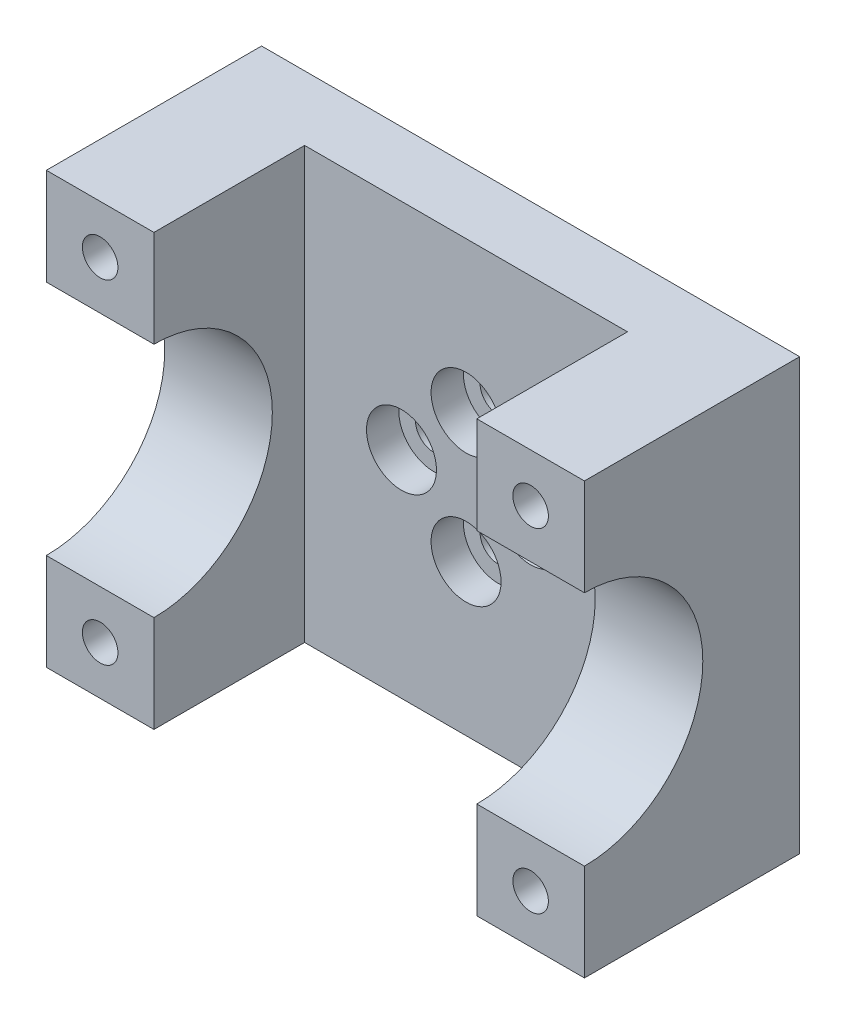
SolidWorks part; units mm, degrees
material "Сплав 2024"
ref_plane "Спереди" through (0, 0, 0) normal (0, 0, 1) x (1, 0, 0)
ref_plane "Сверху" through (0, 0, 0) normal (0, 1, 0) x (1, 0, 0)
ref_plane "Справа" through (0, 0, 0) normal (1, 0, 0) x (0, 0, -1)
sketch "Эскиз1" plane through (0, 0, 0) normal (0, 0, 1) x (1, 0, 0)
  line L1 (0, 0) -> (50, 0)
  line L2 (0, 0) -> (0, 40)
  line L3 (0, 40) -> (50, 40)
  line L4 (50, 0) -> (50, 40)
  dimension "D1" = 50
  dimension "D2" = 40
extrude "Бобышка-Вытянуть1" add sketch "Эскиз1" along normal blind 20
sketch "Эскиз2" plane through (0, 0, 0) normal (-1, 0, 0) x (0, 0, 1)
  line L0 (0, 20) -> (35.6609, 20) construction
  line L1 (0, 40) -> (0, 0) construction
  line L2 (20, 40) -> (20, 0) construction
  line L3 (20, 31) -> (20, 9)
  arc A0 (20, 31) -> (20, 9) centre (20, 20) ccw
  dimension "D1" = 11
extrude "Вырез-Вытянуть1" cut sketch "Эскиз2" against normal through all
sketch "Эскиз3" plane through (0, 0, 20) normal (0, 0, 1) x (1, 0, 0)
  line L0 (25, 40) -> (25, 0) construction
  line L1 (50, 40) -> (0, 40) construction
  line L2 (0, 0) -> (50, 0) construction
  line L3 (0, 20) -> (50, 20) construction
  line L4 (0, 31) -> (0, 9) construction
  line L5 (50, 9) -> (50, 31) construction
  line L6 (0, 40) -> (0, 31) construction
  line L7 (10, 40) -> (40, 40)
  line L8 (10, 40) -> (10, 0)
  line L9 (10, 0) -> (40, 0)
  line L10 (40, 40) -> (40, 0)
  line L11 (10, 40) -> (40, 0) construction
  line L12 (10, 0) -> (40, 40) construction
  point P12 (25, 20)
  dimension "D1" = 10
extrude "Вырез-Вытянуть2" cut sketch "Эскиз3" against normal blind 14
sketch "Эскиз4" plane through (0, 0, 6) normal (0, 0, 1) x (1, 0, 0)
  line L0 (25, 40) -> (25, 0) construction
  line L1 (40, 40) -> (10, 40) construction
  line L2 (10, 0) -> (40, 0) construction
  line L3 (50, 20) -> (0, 20) construction
  line L4 (50, 9) -> (50, 31) construction
  line L5 (0, 31) -> (0, 9) construction
  circle A0 centre (25, 20) radius 6 construction
  dimension "D1" = 12
sketch "Эскиз7" plane through (0, 0, 20) normal (0, 0, 1) x (1, 0, 0)
  line L0 (5, 40) -> (5, 0) construction
  line L1 (10, 40) -> (0, 40) construction
  line L2 (0, 0) -> (10, 0) construction
  line L3 (45, 40) -> (45, 0) construction
  line L4 (50, 40) -> (40, 40) construction
  line L5 (40, 0) -> (50, 0) construction
  line L6 (0, 35.5) -> (50, 35.5) construction
  line L7 (0, 40) -> (0, 31) construction
  line L8 (50, 31) -> (50, 40) construction
  line L10 (0, 4.5) -> (50, 4.5) construction
  line L11 (0, 9) -> (0, 0) construction
  line L12 (50, 0) -> (50, 9) construction
hole_wizard "Цековка для винта с внутренним шестигранником M31" positions "Эскиз6" profile "Эскиз5" counterbore size "M3" standard "Ansi Metric" end condition through all
sketch "Эскиз6" plane through (0, 0, 6) normal (0, 0, 1) x (1, 0, 0)
  line L0 (25, 40) -> (25, 0) construction
  line L1 (50, 20) -> (0, 20) construction
  circle A0 centre (25, 20) radius 6 construction
  point P0 (25, 26)
  point P6 (19, 20)
  point P10 (25, 14)
  point P12 (31, 20)
sketch "Эскиз5" plane through (25, 26, 6) normal (1, 0, 0) x (0, -1, 0)
  line L0 (0, 0) -> (0, 6)
  line L1 (0, 6) -> (1.7, 6)
  line L3 (1.7, 6) -> (1.7, 3)
  line L4 (1.7, 3) -> (3.25, 3)
  line L5 (3.25, 3) -> (3.25, 0)
  line L7 (3.25, 0) -> (0, 0)
  line L11 (0, -6.35) -> (0, 107.95) construction
  dimension "Диаметр сквозного отверстия" = 3.4
  dimension "Глубина сквозного отверстия" = 6
  dimension "Диаметр цековки" = 6.5
  dimension "Глубина цековки" = 3
hole_wizard "Отверстие обработанное метчиком M4x0.71" positions "Эскиз9" profile "Эскиз8" tap size "M4x0.7" standard "Ansi Metric" end condition through all
sketch "Эскиз9" plane through (0, 0, 20) normal (0, 0, 1) x (1, 0, 0)
  line L0 (5, 40) -> (5, 0) construction
  line L1 (0, 35.5) -> (50, 35.5) construction
  line L2 (0, 4.5) -> (50, 4.5) construction
  line L3 (45, 40) -> (45, 0) construction
  point P0 (5, 35.5)
  point P6 (5, 4.5)
  point P10 (45, 4.5)
  point P14 (45, 35.5)
sketch "Эскиз8" plane through (5, 35.5, 20) normal (1, 0, 0) x (0, -1, 0)
  line L0 (0, 0) -> (0, 20)
  line L1 (0, 20) -> (1.65, 20)
  line L2 (1.65, 20) -> (1.65, 0)
  line L5 (1.65, 0) -> (0, 0)
  line L11 (0, -6.35) -> (0, 107.95) construction
  dimension "Диаметр проходного сверла" = 3.3
  dimension "Глубина проходного сверла" = 20
cosmetic thread "Отверстие резьбы1" parameters "D2"=4
cosmetic thread "Отверстие резьбы2" parameters "D2"=4
cosmetic thread "Отверстие резьбы3" parameters "D2"=4
cosmetic thread "Отверстие резьбы4" parameters "D2"=4
